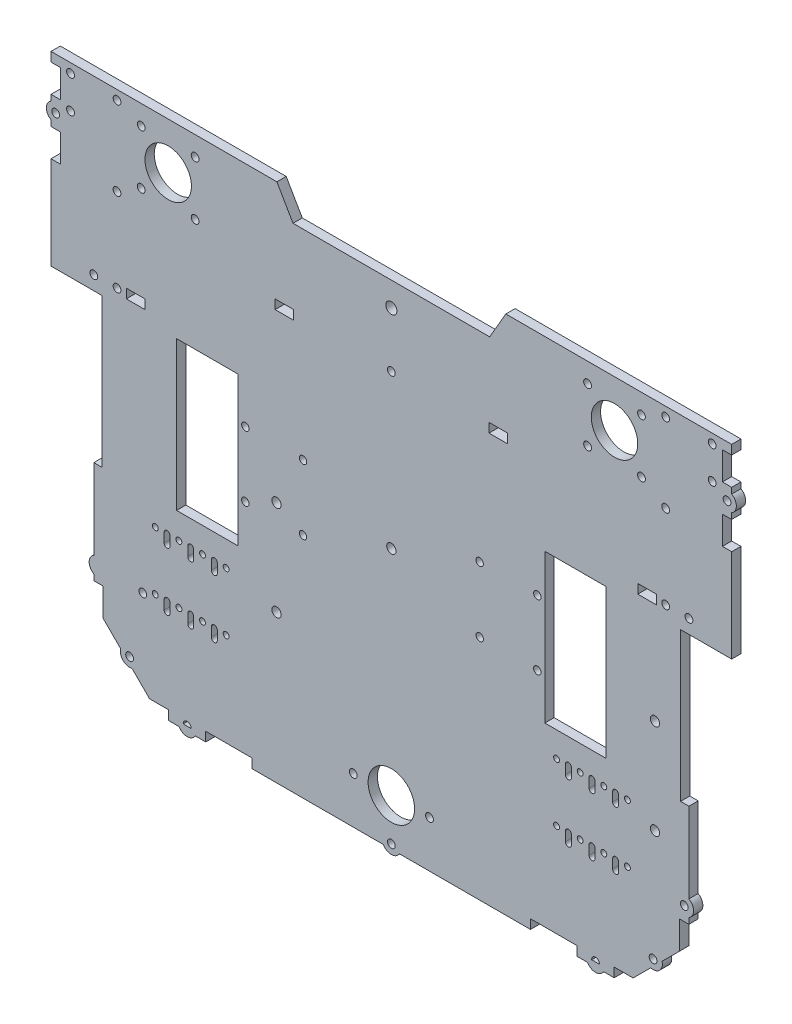
SolidWorks part; units mm, degrees
ref_plane "Front Plane" through (0, 0, 0) normal (0, 0, 1) x (1, 0, 0)
ref_plane "Top Plane" through (0, 0, 0) normal (0, 1, 0) x (1, 0, 0)
ref_plane "Right Plane" through (0, 0, 0) normal (1, 0, 0) x (0, 0, -1)
sketch "Sketch1" plane through (0, 0, 0) normal (0, 0, 1) x (1, 0, 0)
  line L0 (25.4788, 82.9173) -> (-48.0827, -25.4788) construction
  line L1 (0, 0) -> (-320, 0)
  line L2 (0, 0) -> (0, 280)
  line L3 (0, 280) -> (-320, 280)
  line L4 (-320, 0) -> (-320, 280)
  line L5 (-287.2977, 295.1787) -> (-360.8591, 186.7826) construction
  line L6 (25.4788, 82.9173) -> (-287.2977, 295.1787) construction
  line L13 (-184.6572, -15.1656) -> (-182.9535, -19.8663) construction
  line L14 (-182.9535, -19.8663) -> (-121.3306, 2.4686) construction
  line L18 (-114.8924, 10.1204) -> (-184.6572, -15.1656) construction
  line L20 (-48.0827, -25.4788) -> (-360.8591, 186.7826) construction
  line L21 (-46.3981, -22.9964) -> (-359.1745, 189.265) construction
  line L22 (23.7942, 80.4349) -> (-288.9823, 292.6963) construction
  line L23 (-184.6572, -15.1656) -> (-186.361, -10.4648) construction
  line L24 (-186.361, -10.4648) -> (-124.7382, 11.8702) construction
  line L36 (-185.5509, 222.5041) -> (-255.7432, 119.0727) construction
  line L37 (-117.2157, 100.5961) -> (-220.647, 170.7884) construction
  line L38 (-82.1195, 152.3118) -> (-152.3118, 48.8805) construction
  circle A0 centre (-65.5, 65.5) radius 62.5 construction
  circle A17 centre (-272.3627, 205.8845) radius 62.5 construction
  circle A18 centre (-65.5, 65.5) radius 65.5 construction
  circle A22 centre (-168.9314, 135.6923) radius 62.5 construction
  circle A24 centre (-114.8924, 10.1204) radius 74.2059 construction
  circle A27 centre (-114.8924, 10.1204) radius 2.5 construction
  circle A28 centre (-138.3962, 1.6016) radius 1.5 construction
  arc A29 (-121.3306, 2.4686) -> (-124.7382, 11.8702) centre (-114.8924, 10.1204) ccw construction
  point P8 (-320, 246.3436)
  point P9 (-320, 165.4254)
  point P15 (0, 0)
  point P18 (-399.3278, -71.3874)
  point P19 (0, 0)
  point P26 (0, 0)
  point P32 (0, 0)
  point P33 (-297.9462, 157.5259)
  point P34 (-114.3385, 11.0623)
  point P35 (0, 0)
  point P36 (-114.8924, 10.1204)
  dimension "D5" = 5
  dimension "D6" = 5
  dimension "D11" = 125
  dimension "D12" = 280
  dimension "D26" = 125
  dimension "D31" = 125
  dimension "D4" = 5
  dimension "D9" = 10
  dimension "D13" = 320
  dimension "D8" = 3
  dimension "D10" = 3
  dimension "D7" = 25
extrude "Boss-Extrude1" add sketch "Sketch1" along normal blind 5
sketch "Sketch2" plane through (0, 0, 5) normal (0, 0, 1) x (1, 0, 0)
  line L0 (-320, 280) -> (-320, 0) construction
  line L1 (-320, 180) -> (-242.5, 180)
  line L2 (-320, 180) -> (-320, 100)
  line L3 (-320, 100) -> (-242.5, 100)
  line L4 (-242.5, 180) -> (-242.5, 100)
  line L5 (-160, 280) -> (-160, 182.7983) construction
  line L6 (0, 280) -> (-320, 280) construction
  line L7 (-77.5, 180) -> (-77.5, 100)
  line L8 (0, 100) -> (-77.5, 100)
  line L9 (0, 180) -> (0, 100)
  line L10 (0, 180) -> (-77.5, 180)
  point P14 (-320, 140)
  point P15 (-242.5, 140)
  dimension "D1" = 80
  dimension "D2" = 77.5
extrude "Cut-Extrude1" cut sketch "Sketch2" against normal blind 5
sketch "Sketch3" plane through (0, 0, 5) normal (0, 0, 1) x (1, 0, 0)
  line L0 (-242.5, 180) -> (-320, 180) construction
  line L1 (-310.5, 180) -> (-293, 180)
  line L2 (-310.5, 180) -> (-310.5, 100)
  line L3 (-310.5, 100) -> (-293, 100)
  line L4 (-293, 180) -> (-293, 100)
  line L5 (-320, 100) -> (-242.5, 100) construction
  line L6 (-242.5, 100) -> (-242.5, 180) construction
  line L7 (-160, 280) -> (-160, 181.1057) construction
  line L8 (0, 280) -> (-320, 280) construction
  line L9 (-27, 180) -> (-27, 100)
  line L10 (-9.5, 100) -> (-27, 100)
  line L11 (-9.5, 180) -> (-9.5, 100)
  line L12 (-9.5, 180) -> (-27, 180)
  dimension "D1" = 17.5
  dimension "D2" = 68
extrude "Boss-Extrude2" add sketch "Sketch3" against normal blind 5
ref_plane "Plane1" through (-160, 0, 0) normal (1, 0, 0) x (0, 0, -1)
sketch "Sketch9" plane through (0, 0, 0) normal (0, 0, -1) x (-1, 0, 0)
  line L0 (320, 0) -> (0, 0) construction
  line L1 (210, 260) -> (260, 346.6025)
  line L2 (260, 346.6025) -> (210, 433.2051)
  line L3 (210, 433.2051) -> (110, 433.2051)
  line L4 (110, 433.2051) -> (60, 346.6025)
  line L5 (60, 346.6025) -> (110, 260)
  line L6 (110, 260) -> (210, 260)
  line L8 (0, 280) -> (320, 280) construction
  circle A0 centre (160, 346.6025) radius 86.6025 construction
  point P11 (160, 0)
  dimension "D1" = 200
  dimension "D2" = 20
extrude "Cut-Extrude8" cut sketch "Sketch9" against normal blind 5
sketch "Sketch10" plane through (-320, 0, 0) normal (-1, 0, 0) x (0, 0, 1)
  line L4 (0, 280) -> (0, 180)
  line L5 (0, 180) -> (5, 180)
  line L6 (5, 180) -> (5, 280)
  line L7 (5, 280) -> (0, 280)
  line L8 (0, 280) -> (0, 180)
  line L9 (0, 180) -> (5, 180)
  line L10 (5, 180) -> (5, 280)
  line L11 (5, 280) -> (0, 280)
  dimension "D1" = 0
extrude "Boss-Extrude3" add sketch "Sketch10" along normal blind 20
mirror "Mirror2" about plane through (-160, 0, 0) normal (1, 0, 0) of "Boss-Extrude3"
sketch "Sketch5" plane through (0, 0, 5) normal (0, 0, 1) x (1, 0, 0)
  line L0 (20, 280) -> (-98.453, 280) construction
  line L3 (12.5, 257.5) -> (0, 245) construction
  line L4 (0, 245) -> (24.9281, 220.0719) construction
  line L5 (20, 280) -> (20, 180) construction
  circle A1 centre (0, 245) radius 11 construction
  circle A2 centre (12.5, 257.5) radius 2.1
  circle A5 centre (-12.5, 232.5) radius 2.1
  circle A6 centre (-12.5, 187.5) radius 2.1
  circle A7 centre (12.5, 162.5) radius 2.1
  circle A8 centre (-57.5, 187.5) radius 2.1
  circle A9 centre (-82.5, 162.5) radius 2.1
  circle A10 centre (-57.5, 232.5) radius 2.1
  circle A11 centre (-82.5, 257.5) radius 2.1
  circle A12 centre (-12.5, 275) radius 2.1
  circle A13 centre (12.5, 275) radius 2.1
  dimension "D1" = 35
  dimension "D2" = 12.5
  dimension "D3" = 12.5
  dimension "D4" = 22
  dimension "D5" = 4
  dimension "D6" = 4.2
  dimension "D7" = 5
  dimension "D8" = 20
  dimension "D9" = 5
  dimension "D10" = 4.2
  dimension "D11" = 4.2
  dimension "D12" = 12.5
  dimension "D13" = 12.5
extrude "Cut-Extrude9" cut sketch "Sketch5" against normal blind 10 contours A1 | A6 | A12 | A7 | A5 | A2 | A13 region at (-12.5, 232.5, 5) region at (-12.5, 187.5, 5) region at (12.5, 162.5, 5) region at (-12.5, 275, 5)
mirror "Mirror3" about plane through (-160, 0, 0) normal (1, 0, 0) of "Cut-Extrude9"
sketch "Sketch12" plane through (0, 0, 5) normal (0, 0, 1) x (1, 0, 0)
  line L0 (0, 0) -> (0, 100) construction
  line L1 (0, 10) -> (-5, 10)
  line L2 (0, 10) -> (0, 45.2)
  line L3 (0, 45.2) -> (-5, 45.2)
  line L4 (-5, 10) -> (-5, 45.2)
  line L5 (-320, 0) -> (0, 0) construction
  line L6 (-160, -2.75) -> (-160, 2.75) construction
  line L7 (-320, 45.2) -> (-315, 45.2)
  line L8 (-315, 10) -> (-315, 45.2)
  line L9 (-320, 10) -> (-315, 10)
  line L10 (-320, 10) -> (-320, 45.2)
  line L11 (-320, 100) -> (-320, 0) construction
  line L12 (-295, 0) -> (-234.8, 0)
  line L13 (-295, 0) -> (-295, 5)
  line L14 (-295, 5) -> (-234.8, 5)
  line L15 (-234.8, 0) -> (-234.8, 5)
  line L16 (-25, 5) -> (-85.2, 5)
  line L17 (-85.2, 0) -> (-85.2, 5)
  line L18 (-25, 0) -> (-85.2, 0)
  line L19 (-25, 0) -> (-25, 5)
  dimension "D1" = 35.2
  dimension "D2" = 5
  dimension "D3" = 10
  dimension "D4" = 5
  dimension "D5" = 60.2
  dimension "D6" = 25
extrude "Cut-Extrude11" cut sketch "Sketch12" against normal blind 10
sketch "Sketch15" plane through (0, 0, 0) normal (0, 0, -1) x (-1, 0, 0)
  line L0 (242.5, 140) -> (150.9995, 140) construction
  line L1 (242.5, 100) -> (242.5, 180) construction
  line L2 (223, 87.5) -> (223, 97.0195) construction
  line L3 (242.5, 100) -> (77.5, 100) construction
  line L4 (160, 100) -> (160, 101.8451) construction
  line L5 (97, 87.5) -> (97, 97.0195) construction
  line L6 (77.5, 140) -> (169.0005, 140) construction
  circle A0 centre (238.5, 122.5) radius 2
  circle A1 centre (238.5, 157.5) radius 2
  circle A2 centre (207.5, 157.5) radius 2
  circle A3 centre (207.5, 122.5) radius 2
  circle A4 centre (112.5, 122.5) radius 2
  circle A5 centre (112.5, 157.5) radius 2
  circle A6 centre (81.5, 157.5) radius 2
  circle A7 centre (81.5, 122.5) radius 2
  circle A8 centre (160, 140) radius 2.5
  point P6 (242.5, 140)
  dimension "D1" = 4
  dimension "D2" = 4
  dimension "D3" = 17.5
  dimension "D5" = 5
  dimension "D4" = 15.5
extrude "Cut-Extrude13" cut sketch "Sketch15" against normal blind 10
sketch "Sketch16" plane through (0, 0, 0) normal (0, 0, -1) x (-1, 0, 0)
  line L0 (27, 145) -> (9.5, 145) construction
  line L1 (9.5, 65) -> (27, 65) construction
  line L2 (18.25, 145) -> (18.25, 65) construction
  line L3 (18.25, 105) -> (30.55, 105) construction
  line L4 (120, 105) -> (120, 123.3727) construction
  line L5 (221.75, 105) -> (209.45, 105) construction
  circle A4 centre (18.25, 130.5) radius 2.5
  circle A5 centre (18.25, 79.5) radius 2.5
  circle A6 centre (221.75, 79.5) radius 2.5
  circle A7 centre (221.75, 130.5) radius 2.5
  point P12 (18.25, 105)
  dimension "D1" = 5
  dimension "D2" = 25.5
extrude "Cut-Extrude14" cut sketch "Sketch16" against normal blind 10
sketch "Sketch17" plane through (0, 0, 0) normal (0, 0, -1) x (-1, 0, 0)
  line L0 (40, 255) -> (92.7701, 202.2299) construction
  line L1 (-20, 280) -> (98.453, 280) construction
  line L2 (-20, 280) -> (-20, 180) construction
  line L3 (40, 255) -> (-1.2922, 213.7078) construction
  line L4 (160, 260) -> (160, 162.3502) construction
  line L5 (110, 260) -> (210, 260) construction
  line L6 (280, 255) -> (321.2922, 213.7078) construction
  line L7 (280, 255) -> (227.2299, 202.2299) construction
  line L8 (280, 255) -> (321.2922, 213.7078) construction
  line L9 (280, 255) -> (227.2299, 202.2299) construction
  circle A0 centre (40, 255) radius 12.5
  circle A1 centre (54.4957, 240.5043) radius 2.1
  circle A2 centre (25.5043, 269.4957) radius 2.1
  circle A12 centre (54.4957, 269.4957) radius 2.1
  circle A13 centre (25.5043, 240.5043) radius 2.1
  circle A14 centre (54.4957, 240.5043) radius 2.1
  circle A15 centre (25.5043, 269.4957) radius 2.1
  circle A16 centre (25.5043, 240.5043) radius 2.1
  circle A17 centre (54.4957, 269.4957) radius 2.1
  circle A18 centre (265.5043, 269.4957) radius 2.1
  circle A19 centre (294.4957, 240.5043) radius 2.1
  circle A20 centre (294.4957, 269.4957) radius 2.1
  circle A21 centre (265.5043, 240.5043) radius 2.1
  circle A22 centre (294.4957, 240.5043) radius 2.1
  circle A23 centre (265.5043, 269.4957) radius 2.1
  circle A24 centre (280, 255) radius 12.5
  circle A25 centre (265.5043, 240.5043) radius 2.1
  circle A26 centre (294.4957, 269.4957) radius 2.1
  dimension "D1" = 25
  dimension "D2" = 4.2
  dimension "D3" = 20.5
  dimension "D4" = 25
  dimension "D5" = 60
  dimension "D6" = 45
  dimension "D7" = 4
extrude "Cut-Extrude15" cut sketch "Sketch17" against normal blind 5 contours A13 | A0 | A13 | A12 | A1 | A24 | A20 | A19 | A21 | A2 | A18 region at (-40, 255, 0) region at (-54.4957, 240.5043, 0) region at (-54.4957, 269.4957, 0) region at (-25.5043, 240.5043, 0) region at (-294.4957, 240.5043, 0) region at (-294.4957, 269.4957, 0) region at (-265.5043, 240.5043, 0) region at (-280, 255, 0)
sketch "Sketch18" plane through (0, 0, 5) normal (0, 0, 1) x (1, 0, 0)
  line L0 (-315, 30) -> (-290, 5)
  line L1 (-315, 10) -> (-315, 45.2) construction
  line L2 (-234.8, 5) -> (-295, 5) construction
  line L3 (-290, 5) -> (-315, 5)
  line L4 (-315, 5) -> (-315, 30)
  line L5 (-315, 10) -> (-320, 10)
  line L6 (-320, 10) -> (-320, 0)
  line L7 (-320, 0) -> (-295, 0)
  line L8 (-295, 0) -> (-295, 5)
  line L9 (-160, -2.75) -> (-160, 2.75) construction
  line L10 (-5, 5) -> (-5, 30)
  line L11 (-5, 30) -> (-30, 5)
  line L12 (-25, 0) -> (-25, 5)
  line L13 (0, 0) -> (-25, 0)
  line L14 (0, 10) -> (0, 0)
  line L15 (-5, 10) -> (0, 10)
  line L16 (-30, 5) -> (-5, 5)
  dimension "D1" = 25
  dimension "D2" = 25
extrude "Cut-Extrude17" cut sketch "Sketch18" against normal blind 10 contours L4 L3 L0 | L7 L8 L3 L4 L5 L6 | L11 L16 L10 | L16 L12 L13 L14 L15 L10 region at (-306.6667, 13.3333, 5) region at (-309.1667, 3.3333, 5) region at (-13.3333, 13.3333, 5) region at (-10.8333, 3.3333, 5)
sketch "Sketch19" plane through (0, 0, 0) normal (0, 0, -1) x (-1, 0, 0)
  line L0 (234.8, 0) -> (85.2, 0) construction
  line L1 (166.1126, 25) -> (84.2471, 25) construction
  line L2 (160, 25) -> (160, 31.0152) construction
  circle A0 centre (160, 25) radius 12.5
  circle A2 centre (139.5, 25) radius 2.1
  circle A4 centre (180.5, 25) radius 2.1
  point P4 (160, 0)
  dimension "D1" = 25
  dimension "D2" = 25
  dimension "D3" = 4.2
  dimension "D4" = 20.5
extrude "Cut-Extrude18" cut sketch "Sketch19" against normal blind 10
sketch "Sketch21" plane through (-340, 0, 0) normal (-1, 0, 0) x (0, 0, 1)
  line L4 (5, 280) -> (0, 280)
  line L5 (0, 280) -> (0, 180)
  line L6 (0, 180) -> (5, 180)
  line L7 (5, 180) -> (5, 280)
  line L8 (5, 280) -> (0, 280)
  line L9 (0, 280) -> (0, 180)
  line L10 (0, 180) -> (5, 180)
  line L11 (5, 180) -> (5, 280)
  dimension "D1" = 0
extrude "Cut-Extrude20" cut sketch "Sketch21" against normal blind 3
sketch "Sketch22" plane through (20, 0, 0) normal (1, 0, 0) x (0, 0, -1)
  line L4 (0, 280) -> (-5, 280)
  line L5 (-5, 280) -> (-5, 180)
  line L6 (-5, 180) -> (0, 180)
  line L7 (0, 180) -> (0, 280)
  line L8 (0, 280) -> (-5, 280)
  line L9 (-5, 280) -> (-5, 180)
  line L10 (-5, 180) -> (0, 180)
  line L11 (0, 180) -> (0, 280)
  dimension "D1" = 0
extrude "Cut-Extrude21" cut sketch "Sketch22" against normal blind 3
sketch "Sketch23" plane through (0, 0, 0) normal (0, 0, -1) x (-1, 0, 0)
  line L0 (234.8, 0) -> (85.2, 0) construction
  line L1 (164.3301, 0) -> (155.6699, 0) construction
  circle A0 centre (160, 2.5) radius 2.1
  arc A1 (164.3301, 0) -> (155.6699, 0) centre (160, 2.5) cw construction
  point P5 (160, 0)
  dimension "D1" = 4.2
  dimension "D2" = 2.5
  dimension "D3" = 5
extrude "Cut-Extrude22" cut sketch "Sketch23" against normal blind 10
sketch "Sketch24" plane through (0, 0, 0) normal (0, 0, -1) x (-1, 0, 0)
  line L0 (234.8, 0) -> (85.2, 0) construction
  line L1 (164.3301, 0) -> (155.6699, 0)
  arc A0 (164.3301, 0) -> (155.6699, 0) centre (160, 2.5) cw
  dimension "D1" = 5
extrude "Boss-Extrude4" add sketch "Sketch24" against normal blind 5
sketch "Sketch25" plane through (-17.5, 17.5, 0) normal (0.7071, -0.7071, 0) x (0, 0, -1)
  line L1 (12.2918, -37.7929) -> (-20.8331, -37.7929)
  line L2 (12.2918, -37.7929) -> (12.2918, 35.3561)
  line L3 (12.2918, 35.3561) -> (-20.8331, 35.3561)
  line L4 (-20.8331, -37.7929) -> (-20.8331, 35.3561)
ref_plane "Plane2" through (-160, 0, 0) normal (1, 0, 0) x (0, 0, -1)
sketch "Sketch26" plane through (0, 5, 0) normal (0, -1, 0) x (1, 0, 0)
  line L1 (-60.2, 5) -> (-40.2, 5)
  line L2 (-60.2, 5) -> (-60.2, 0)
  line L3 (-60.2, 0) -> (-40.2, 0)
  line L4 (-40.2, 5) -> (-40.2, 0)
  line L7 (-85.2, 0) -> (-85.2, 5) construction
  line L8 (-164.3301, 5) -> (-164.3301, 0) construction
  line L12 (-155.6699, 5) -> (-155.6699, 0) construction
  line L13 (-164.3301, 5) -> (-164.3301, 0) construction
  line L14 (-155.6699, 5) -> (-155.6699, 0) construction
  line L16 (-155.6699, 2.5) -> (-164.3301, 2.5) construction
  line L17 (-164.3301, 2.5) -> (-160, 2.5) construction
  line L18 (-160, 2.5) -> (-160, 11.7083) construction
  line L19 (-279.8, 5) -> (-279.8, 0)
  line L20 (-259.8, 0) -> (-279.8, 0)
  line L21 (-259.8, 5) -> (-259.8, 0)
  line L22 (-259.8, 5) -> (-279.8, 5)
  line M6 (-30, 5) -> (-85.2, 5)
  line M8 (-85.2, 0) -> (-30, 0)
  dimension "D1" = 20
  dimension "D2" = 25
extrude "Boss-Extrude5" add sketch "Sketch26" along normal blind 5 contours L4 L2 M6 M8 | L21 L22 L19 L20 region at (-50.2, 5, 2.5) region at (-269.8, 5, 2.5)
sketch "Sketch27" plane through (0, 0, 0) normal (0, 0, -1) x (-1, 0, 0)
  line L2 (160, 2.5) -> (160, 6.3371) construction
  circle A0 centre (50.2, 2.5) radius 2.1
  circle A1 centre (269.8, 2.5) radius 2.1
  dimension "D3" = 4.2
extrude "Cut-Extrude24" cut sketch "Sketch27" against normal blind 5
sketch "Sketch29" plane through (0, 0, 0) normal (0, 0, -1) x (-1, 0, 0)
  line L1 (274.7978, 2.3518) -> (264.8022, 2.3518)
  line L2 (160, 2.75) -> (160, -2.75) construction
  line L3 (45.2022, 2.3518) -> (55.1978, 2.3518)
  arc A0 (264.8022, 2.3518) -> (274.7978, 2.3518) centre (269.8, 2.5) ccw
  arc A1 (55.1978, 2.3518) -> (45.2022, 2.3518) centre (50.2, 2.5) cw
  dimension "D1" = 5
extrude "Boss-Extrude7" add sketch "Sketch29" against normal blind 5
sketch "Sketch30" plane through (-9.5, 0, 0) normal (1, 0, 0) x (0, 0, -1)
  line L4 (-5, 180) -> (-5, 100)
  line L6 (-5, 180) -> (-5, 100)
  line L12 (-5, 100) -> (0, 100)
  line L14 (-5, 100) -> (0, 100)
  line L16 (0, 100) -> (0, 180)
  line L17 (0, 100) -> (0, 180)
  line L18 (0, 180) -> (-5, 180)
  line L19 (0, 180) -> (-5, 180)
  dimension "D1" = 0
extrude "Boss-Extrude8" add sketch "Sketch30" along normal blind 5
sketch "Sketch31" plane through (-310.5, 0, 0) normal (-1, 0, 0) x (0, 0, 1)
  line L4 (5, 100) -> (5, 180)
  line L5 (5, 180) -> (0, 180)
  line L6 (0, 180) -> (0, 100)
  line L8 (5, 100) -> (5, 180)
  line L10 (0, 180) -> (0, 100)
  line L12 (5, 180) -> (0, 180)
  line L14 (0, 100) -> (5, 100)
  line L15 (0, 100) -> (5, 100)
  dimension "D1" = 0
extrude "Boss-Extrude9" add sketch "Sketch31" along normal blind 5
sketch "Sketch32" plane through (0, 0, 0) normal (0, 0, -1) x (-1, 0, 0)
  line L0 (5, 30) -> (30, 5) construction
  line L1 (17.5, 17.5) -> (24.3538, 24.3538) construction
  circle A0 centre (19.2678, 19.2678) radius 2.1
  dimension "D1" = 4.2
  dimension "D2" = 2.5
extrude "Cut-Extrude25" cut sketch "Sketch32" against normal blind 5
sketch "Sketch33" plane through (0, 0, 0) normal (0, 0, -1) x (-1, 0, 0)
  line L0 (5, 30) -> (30, 5) construction
  line L1 (20.5619, 14.4381) -> (14.4381, 20.5619)
  arc A0 (20.5619, 14.4381) -> (14.4381, 20.5619) centre (19.2678, 19.2678) cw
  dimension "D1" = 5
extrude "Boss-Extrude10" add sketch "Sketch33" against normal blind 5
ref_plane "Plane3" through (-160, 0, 0) normal (-1, 0, 0) x (0, 0, 1)
mirror "Mirror4" about plane through (-160, 0, 0) normal (-1, 0, 0) of "Boss-Extrude10", "Cut-Extrude25"
sketch "Sketch34" plane through (0, 0, 5) normal (0, 0, 1) x (1, 0, 0)
  line L2 (-110, 260) -> (-210, 260) construction
  circle A0 centre (-160, 252) radius 3
  point P4 (-160, 260)
  dimension "D1" = 6
  dimension "D3" = 8
extrude "Cut-Extrude26" cut sketch "Sketch34" against normal blind 5
sketch "Sketch35" plane through (0, 0, 0) normal (0, 0, -1) x (-1, 0, 0)
  line L0 (110, 260) -> (210, 260) construction
  line L1 (97.5, 225) -> (107.5, 225)
  line L2 (97.5, 225) -> (97.5, 220)
  line L3 (97.5, 220) -> (107.5, 220)
  line L4 (107.5, 225) -> (107.5, 220)
  line L5 (-17, 180) -> (-17, 280) construction
  line L6 (160, 260) -> (160, 169.3293) construction
  line L7 (212.5, 225) -> (212.5, 220)
  line L8 (222.5, 220) -> (212.5, 220)
  line L9 (222.5, 225) -> (222.5, 220)
  line L10 (222.5, 225) -> (212.5, 225)
  line L11 (107.5, 222.5) -> (212.5, 222.5) construction
  circle A0 centre (160, 222.5) radius 2.1
  point P6 (97.5, 222.5)
  dimension "D5" = 4.2
  dimension "D1" = 35
  dimension "D2" = 114.5
  dimension "D3" = 10
  dimension "D4" = 5
extrude "Cut-Extrude27" cut sketch "Sketch35" against normal blind 5
sketch "Sketch37" plane through (0, 45.2, 0) normal (0, -1, 0) x (1, 0, 0)
  line L4 (0, 0) -> (0, 5)
  line L5 (0, 5) -> (-5, 5)
  line L6 (-5, 5) -> (-5, 0)
  line L7 (-5, 0) -> (0, 0)
  line L8 (0, 0) -> (0, 5)
  line L9 (0, 5) -> (-5, 5)
  line L10 (-5, 5) -> (-5, 0)
  line L11 (-5, 0) -> (0, 0)
  dimension "D1" = 0
extrude "Boss-Extrude11" add sketch "Sketch37" along normal blind 0.2
sketch "Sketch38" plane through (0, 45.2, 0) normal (0, -1, 0) x (1, 0, 0)
  line L4 (-315, 0) -> (-315, 5)
  line L5 (-315, 5) -> (-320, 5)
  line L6 (-320, 5) -> (-320, 0)
  line L7 (-320, 0) -> (-315, 0)
  line L8 (-315, 0) -> (-315, 5)
  line L9 (-315, 5) -> (-320, 5)
  line L10 (-320, 5) -> (-320, 0)
  line L11 (-320, 0) -> (-315, 0)
  dimension "D1" = 0
extrude "Boss-Extrude12" add sketch "Sketch38" along normal blind 0.2
sketch "Sketch39" plane through (0, 0, 0) normal (0, 0, -1) x (-1, 0, 0)
  line L0 (5, 45) -> (0, 45) construction
  line L1 (0, 45) -> (0, 100) construction
  line L2 (148.069, 28.7284) -> (148.069, 57.8422) construction
  line L3 (0, 56.8301) -> (0, 48.1699) construction
  line L4 (296.138, 56.8301) -> (296.138, 48.1699) construction
  circle A0 centre (2.5, 52.5) radius 2.1
  circle A1 centre (160, 25) radius 12.5 construction
  circle A2 centre (293.638, 52.5) radius 2.1
  arc A3 (0, 48.1699) -> (0, 56.8301) centre (2.5, 52.5) cw construction
  arc A4 (296.138, 48.1699) -> (296.138, 56.8301) centre (293.638, 52.5) ccw construction
  dimension "D1" = 4.2
  dimension "D2" = 7.5
  dimension "D3" = 2.5
  dimension "D4" = 5
extrude "Cut-Extrude28" cut sketch "Sketch39" against normal blind 5
sketch "Sketch40" plane through (0, 0, 0) normal (0, 0, -1) x (-1, 0, 0)
  line L0 (0, 45) -> (0, 100) construction
  line L1 (0, 56.8301) -> (0, 48.1699)
  line L2 (160, 37.5) -> (160, 52.5) construction
  line L3 (320, 56.8301) -> (320, 48.1699)
  arc A0 (0, 48.1699) -> (0, 56.8301) centre (2.5, 52.5) cw
  circle A1 centre (160, 25) radius 12.5 construction
  arc A2 (320, 48.1699) -> (320, 56.8301) centre (317.5, 52.5) ccw
  dimension "D1" = 5
extrude "Boss-Extrude13" add sketch "Sketch40" against normal blind 5
sketch "Sketch42" plane through (0, 0, 5) normal (0, 0, 1) x (1, 0, 0)
  line L0 (-81.5, 157.5) -> (-81.5, 122.5) construction
  line L1 (-81.5, 140) -> (-63.225, 140) construction
  line L2 (-71.1625, 86.5) -> (-71.1625, 55.25) construction
  line L3 (-71.1625, 70.875) -> (-81.5, 70.875) construction
  line L4 (-64.8125, 86.5) -> (-64.8125, 55.25) construction
  line L5 (-58.4625, 86.5) -> (-58.4625, 55.25) construction
  line L6 (-52.1125, 55.25) -> (-52.1125, 86.5) construction
  line L7 (-45.7625, 86.5) -> (-45.7625, 55.25) construction
  line L8 (-39.4125, 55.25) -> (-39.4125, 86.5) construction
  line L9 (-33.0625, 86.5) -> (-33.0625, 55.25) construction
  line L10 (17, 280) -> (17, 180) construction
  line L13 (17, 280) -> (-98.453, 280) construction
  line L14 (-64.8125, 86.5) -> (-64.8125, 81.5) construction
  line L15 (-63.225, 86.5) -> (-63.225, 81.5)
  line L16 (-66.4, 86.5) -> (-66.4, 81.5)
  line L17 (-52.1125, 86.5) -> (-52.1125, 81.5) construction
  line L18 (-50.525, 86.5) -> (-50.525, 81.5)
  line L19 (-53.7, 86.5) -> (-53.7, 81.5)
  line L20 (-39.4125, 86.5) -> (-39.4125, 81.5) construction
  line L21 (-37.825, 86.5) -> (-37.825, 81.5)
  line L22 (-41, 86.5) -> (-41, 81.5)
  line L23 (-64.8125, 55.25) -> (-64.8125, 50.25) construction
  line L24 (-63.225, 55.25) -> (-63.225, 50.25)
  line L25 (-66.4, 55.25) -> (-66.4, 50.25)
  line L26 (-52.1125, 55.25) -> (-52.1125, 50.25) construction
  line L27 (-50.525, 55.25) -> (-50.525, 50.25)
  line L28 (-53.7, 55.25) -> (-53.7, 50.25)
  line L29 (-39.4125, 55.25) -> (-39.4125, 50.25) construction
  line L30 (-37.825, 55.25) -> (-37.825, 50.25)
  line L31 (-41, 55.25) -> (-41, 50.25)
  line L32 (-160, -2.75) -> (-160, 2.75) construction
  line L33 (-286.9375, 86.5) -> (-286.9375, 55.25) construction
  line L34 (-280.5875, 55.25) -> (-280.5875, 86.5) construction
  line L35 (-274.2375, 86.5) -> (-274.2375, 55.25) construction
  line L36 (-267.8875, 55.25) -> (-267.8875, 86.5) construction
  line L37 (-261.5375, 86.5) -> (-261.5375, 55.25) construction
  line L38 (-255.1875, 86.5) -> (-255.1875, 55.25) construction
  line L39 (-248.8375, 70.875) -> (-238.5, 70.875) construction
  line L40 (-248.8375, 86.5) -> (-248.8375, 55.25) construction
  line L41 (-280.5875, 55.25) -> (-280.5875, 50.25) construction
  line L42 (-282.175, 55.25) -> (-282.175, 50.25)
  line L43 (-279, 55.25) -> (-279, 50.25)
  line L44 (-267.8875, 55.25) -> (-267.8875, 50.25) construction
  line L45 (-269.475, 55.25) -> (-269.475, 50.25)
  line L46 (-266.3, 55.25) -> (-266.3, 50.25)
  line L47 (-255.1875, 55.25) -> (-255.1875, 50.25) construction
  line L48 (-256.775, 55.25) -> (-256.775, 50.25)
  line L49 (-253.6, 55.25) -> (-253.6, 50.25)
  line L50 (-280.5875, 86.5) -> (-280.5875, 81.5) construction
  line L51 (-282.175, 86.5) -> (-282.175, 81.5)
  line L52 (-279, 86.5) -> (-279, 81.5)
  line L53 (-267.8875, 86.5) -> (-267.8875, 81.5) construction
  line L54 (-269.475, 86.5) -> (-269.475, 81.5)
  line L55 (-266.3, 86.5) -> (-266.3, 81.5)
  line L56 (-255.1875, 86.5) -> (-255.1875, 81.5) construction
  line L57 (-256.775, 86.5) -> (-256.775, 81.5)
  line L58 (-253.6, 86.5) -> (-253.6, 81.5)
  arc A2 (-63.225, 86.5) -> (-66.4, 86.5) centre (-64.8125, 86.5) ccw
  arc A3 (-66.4, 81.5) -> (-63.225, 81.5) centre (-64.8125, 81.5) ccw
  arc A4 (-50.525, 86.5) -> (-53.7, 86.5) centre (-52.1125, 86.5) ccw
  arc A5 (-53.7, 81.5) -> (-50.525, 81.5) centre (-52.1125, 81.5) ccw
  arc A6 (-37.825, 86.5) -> (-41, 86.5) centre (-39.4125, 86.5) ccw
  arc A7 (-41, 81.5) -> (-37.825, 81.5) centre (-39.4125, 81.5) ccw
  arc A8 (-63.225, 55.25) -> (-66.4, 55.25) centre (-64.8125, 55.25) ccw
  arc A9 (-66.4, 50.25) -> (-63.225, 50.25) centre (-64.8125, 50.25) ccw
  arc A10 (-50.525, 55.25) -> (-53.7, 55.25) centre (-52.1125, 55.25) ccw
  arc A11 (-53.7, 50.25) -> (-50.525, 50.25) centre (-52.1125, 50.25) ccw
  arc A12 (-37.825, 55.25) -> (-41, 55.25) centre (-39.4125, 55.25) ccw
  arc A13 (-41, 50.25) -> (-37.825, 50.25) centre (-39.4125, 50.25) ccw
  arc A14 (-259.95, 86.5) -> (-263.125, 86.5) centre (-261.5375, 86.5) cw
  arc A15 (-263.125, 86.5) -> (-259.95, 86.5) centre (-261.5375, 86.5) cw
  arc A16 (-253.6, 86.5) -> (-256.775, 86.5) centre (-255.1875, 86.5) cw
  arc A17 (-256.775, 86.5) -> (-253.6, 86.5) centre (-255.1875, 86.5) cw
  arc A18 (-247.25, 86.5) -> (-250.425, 86.5) centre (-248.8375, 86.5) cw
  arc A19 (-250.425, 86.5) -> (-247.25, 86.5) centre (-248.8375, 86.5) cw
  arc A20 (-269.475, 86.5) -> (-266.3, 86.5) centre (-267.8875, 86.5) cw
  arc A21 (-266.3, 86.5) -> (-269.475, 86.5) centre (-267.8875, 86.5) cw
  arc A22 (-275.825, 86.5) -> (-272.65, 86.5) centre (-274.2375, 86.5) cw
  arc A23 (-272.65, 86.5) -> (-275.825, 86.5) centre (-274.2375, 86.5) cw
  arc A24 (-282.175, 86.5) -> (-279, 86.5) centre (-280.5875, 86.5) cw
  arc A25 (-279, 86.5) -> (-282.175, 86.5) centre (-280.5875, 86.5) cw
  arc A26 (-285.35, 86.5) -> (-288.525, 86.5) centre (-286.9375, 86.5) cw
  arc A27 (-288.525, 86.5) -> (-285.35, 86.5) centre (-286.9375, 86.5) cw
  arc A28 (-69.575, 55.25) -> (-72.75, 55.25) centre (-71.1625, 55.25) ccw
  arc A29 (-72.75, 55.25) -> (-69.575, 55.25) centre (-71.1625, 55.25) ccw
  arc A30 (-63.225, 55.25) -> (-66.4, 55.25) centre (-64.8125, 55.25) ccw
  arc A31 (-66.4, 55.25) -> (-63.225, 55.25) centre (-64.8125, 55.25) ccw
  arc A32 (-56.875, 55.25) -> (-60.05, 55.25) centre (-58.4625, 55.25) ccw
  arc A33 (-60.05, 55.25) -> (-56.875, 55.25) centre (-58.4625, 55.25) ccw
  arc A34 (-50.525, 55.25) -> (-53.7, 55.25) centre (-52.1125, 55.25) ccw
  arc A35 (-53.7, 55.25) -> (-50.525, 55.25) centre (-52.1125, 55.25) ccw
  arc A36 (-44.175, 55.25) -> (-47.35, 55.25) centre (-45.7625, 55.25) ccw
  arc A37 (-47.35, 55.25) -> (-44.175, 55.25) centre (-45.7625, 55.25) ccw
  arc A38 (-37.825, 55.25) -> (-41, 55.25) centre (-39.4125, 55.25) ccw
  arc A39 (-41, 55.25) -> (-37.825, 55.25) centre (-39.4125, 55.25) ccw
  arc A40 (-31.475, 55.25) -> (-34.65, 55.25) centre (-33.0625, 55.25) ccw
  arc A41 (-34.65, 55.25) -> (-31.475, 55.25) centre (-33.0625, 55.25) ccw
  arc A42 (-31.475, 86.5) -> (-34.65, 86.5) centre (-33.0625, 86.5) ccw
  arc A43 (-34.65, 86.5) -> (-31.475, 86.5) centre (-33.0625, 86.5) ccw
  arc A44 (-41, 86.5) -> (-37.825, 86.5) centre (-39.4125, 86.5) ccw
  arc A45 (-37.825, 86.5) -> (-41, 86.5) centre (-39.4125, 86.5) ccw
  arc A46 (-47.35, 86.5) -> (-44.175, 86.5) centre (-45.7625, 86.5) ccw
  arc A47 (-44.175, 86.5) -> (-47.35, 86.5) centre (-45.7625, 86.5) ccw
  arc A48 (-53.7, 86.5) -> (-50.525, 86.5) centre (-52.1125, 86.5) ccw
  arc A49 (-50.525, 86.5) -> (-53.7, 86.5) centre (-52.1125, 86.5) ccw
  arc A50 (-69.575, 86.5) -> (-72.75, 86.5) centre (-71.1625, 86.5) ccw
  arc A51 (-72.75, 86.5) -> (-69.575, 86.5) centre (-71.1625, 86.5) ccw
  arc A52 (-63.225, 86.5) -> (-66.4, 86.5) centre (-64.8125, 86.5) ccw
  arc A53 (-66.4, 86.5) -> (-63.225, 86.5) centre (-64.8125, 86.5) ccw
  arc A54 (-56.875, 86.5) -> (-60.05, 86.5) centre (-58.4625, 86.5) ccw
  arc A55 (-60.05, 86.5) -> (-56.875, 86.5) centre (-58.4625, 86.5) ccw
  arc A56 (-285.35, 55.25) -> (-288.525, 55.25) centre (-286.9375, 55.25) cw
  arc A57 (-288.525, 55.25) -> (-285.35, 55.25) centre (-286.9375, 55.25) cw
  arc A58 (-279, 55.25) -> (-282.175, 55.25) centre (-280.5875, 55.25) cw
  arc A59 (-282.175, 55.25) -> (-279, 55.25) centre (-280.5875, 55.25) cw
  arc A60 (-272.65, 55.25) -> (-275.825, 55.25) centre (-274.2375, 55.25) cw
  arc A61 (-275.825, 55.25) -> (-272.65, 55.25) centre (-274.2375, 55.25) cw
  arc A62 (-266.3, 55.25) -> (-269.475, 55.25) centre (-267.8875, 55.25) cw
  arc A63 (-269.475, 55.25) -> (-266.3, 55.25) centre (-267.8875, 55.25) cw
  arc A64 (-259.95, 55.25) -> (-263.125, 55.25) centre (-261.5375, 55.25) cw
  arc A65 (-263.125, 55.25) -> (-259.95, 55.25) centre (-261.5375, 55.25) cw
  arc A66 (-253.6, 55.25) -> (-256.775, 55.25) centre (-255.1875, 55.25) cw
  arc A67 (-256.775, 55.25) -> (-253.6, 55.25) centre (-255.1875, 55.25) cw
  arc A68 (-247.25, 55.25) -> (-250.425, 55.25) centre (-248.8375, 55.25) cw
  arc A69 (-250.425, 55.25) -> (-247.25, 55.25) centre (-248.8375, 55.25) cw
  arc A70 (-282.175, 55.25) -> (-279, 55.25) centre (-280.5875, 55.25) cw
  arc A71 (-279, 50.25) -> (-282.175, 50.25) centre (-280.5875, 50.25) cw
  arc A72 (-269.475, 55.25) -> (-266.3, 55.25) centre (-267.8875, 55.25) cw
  arc A73 (-266.3, 50.25) -> (-269.475, 50.25) centre (-267.8875, 50.25) cw
  arc A74 (-256.775, 55.25) -> (-253.6, 55.25) centre (-255.1875, 55.25) cw
  arc A75 (-253.6, 50.25) -> (-256.775, 50.25) centre (-255.1875, 50.25) cw
  arc A76 (-282.175, 86.5) -> (-279, 86.5) centre (-280.5875, 86.5) cw
  arc A77 (-279, 81.5) -> (-282.175, 81.5) centre (-280.5875, 81.5) cw
  arc A78 (-269.475, 86.5) -> (-266.3, 86.5) centre (-267.8875, 86.5) cw
  arc A79 (-266.3, 81.5) -> (-269.475, 81.5) centre (-267.8875, 81.5) cw
  arc A80 (-256.775, 86.5) -> (-253.6, 86.5) centre (-255.1875, 86.5) cw
  arc A81 (-253.6, 81.5) -> (-256.775, 81.5) centre (-255.1875, 81.5) cw
  point P22 (-64.8125, 70.875)
  point P23 (-58.4625, 70.875)
  point P28 (-52.1125, 70.875)
  point P29 (-45.7625, 70.875)
  point P34 (-39.4125, 70.875)
  point P35 (-33.0625, 70.875)
  point P52 (-64.8125, 84)
  point P70 (-52.1125, 84)
  point P86 (-39.4125, 84)
  point P92 (-64.8125, 52.75)
  point P98 (-52.1125, 52.75)
  point P104 (-39.4125, 52.75)
  point P158 (-280.5875, 52.75)
  point P162 (-267.8875, 52.75)
  point P166 (-255.1875, 52.75)
  point P170 (-280.5875, 84)
  point P174 (-267.8875, 84)
  point P178 (-255.1875, 84)
  dimension "D1" = 1.5875
  dimension "D10" = 31.25
  dimension "D2" = 36
  dimension "D3" = 50.0625
  dimension "D4" = 56.4125
  dimension "D5" = 62.7625
  dimension "D6" = 69.1125
  dimension "D7" = 75.4625
  dimension "D8" = 81.8125
  dimension "D9" = 88.1625
  dimension "D11" = 5
  dimension "D12" = 5
extrude "Cut-Extrude29" cut sketch "Sketch42" against normal blind 10 contours A6 A44 | A44 L22 A7 L21 | A46 A47 | A4 A48 | A54 A55 | A2 A53 | A50 A51 | A53 L16 A3 L15 | A48 L19 A5 L18 | A43 A42 | A41 A40 | L30 A13 L31 A12 | A37 A36 | L28 A11 L27 A10 | A33 A32 | L25 A9 L24 A8 | A29 A28 region at (-64.8125, 86.5, 5) region at (-64.8125, 82.7532, 5) region at (-52.1125, 86.5, 5) region at (-52.1125, 82.7532, 5) region at (-39.4125, 86.5, 5) region at (-39.4125, 82.7532, 5) region at (-45.7625, 86.5, 5) region at (-71.1625, 86.5, 5) region at (-58.4625, 86.5, 5)
sketch "Sketch43" plane through (-337, 0, 0) normal (-1, 0, 0) x (0, 0, 1)
  line L4 (5, 180) -> (5, 280)
  line L5 (5, 280) -> (0, 280)
  line L6 (0, 280) -> (0, 180)
  line L7 (0, 180) -> (5, 180)
  line L8 (5, 180) -> (5, 280)
  line L9 (5, 280) -> (0, 280)
  line L10 (0, 280) -> (0, 180)
  line L11 (0, 180) -> (5, 180)
  dimension "D1" = 0
extrude "Boss-Extrude14" add sketch "Sketch43" along normal blind 6
sketch "Sketch44" plane through (17, 0, 0) normal (1, 0, 0) x (0, 0, -1)
  line L4 (0, 180) -> (0, 280)
  line L5 (0, 280) -> (-5, 280)
  line L6 (-5, 280) -> (-5, 180)
  line L7 (-5, 180) -> (0, 180)
  line L8 (0, 180) -> (0, 280)
  line L9 (0, 280) -> (-5, 280)
  line L10 (-5, 280) -> (-5, 180)
  line L11 (-5, 180) -> (0, 180)
  dimension "D1" = 0
extrude "Boss-Extrude15" add sketch "Sketch44" along normal blind 6
sketch "Sketch45" plane through (0, 280, 0) normal (0, 1, 0) x (1, 0, 0)
  line L4 (-221.547, 0) -> (-343, 0)
  line L5 (-343, 0) -> (-343, -5)
  line L6 (-343, -5) -> (-221.547, -5)
  line L7 (-221.547, -5) -> (-221.547, 0)
  line L8 (-221.547, 0) -> (-343, 0)
  line L9 (-343, 0) -> (-343, -5)
  line L10 (-343, -5) -> (-221.547, -5)
  line L11 (-221.547, -5) -> (-221.547, 0)
  dimension "D1" = 0
extrude "Boss-Extrude16" [suppressed] add sketch "Sketch45" along normal blind 6
sketch "Sketch46" plane through (0, 280, 0) normal (0, 1, 0) x (1, 0, 0)
  line L4 (-98.453, -5) -> (23, -5)
  line L5 (23, -5) -> (23, 0)
  line L6 (23, 0) -> (-98.453, 0)
  line L7 (-98.453, 0) -> (-98.453, -5)
  line L8 (-98.453, -5) -> (23, -5)
  line L9 (23, -5) -> (23, 0)
  line L10 (23, 0) -> (-98.453, 0)
  line L11 (-98.453, 0) -> (-98.453, -5)
  dimension "D1" = 0
extrude "Boss-Extrude17" [suppressed] add sketch "Sketch46" along normal blind 6
sketch "Sketch47" [suppressed] plane through (0, 0, 5) normal (0, 0, 1) x (1, 0, 0)
  line L0 (-181.547, 210) -> (-185.0111, 216)
  line L1 (-263, 216) -> (-181.547, 216) construction
  line L2 (-185.0111, 216) -> (-181.547, 216)
  line L3 (-181.547, 216) -> (-181.547, 210)
  line L4 (-120, 182) -> (-120, 205.4993) construction
  line L5 (-58.453, 216) -> (-58.453, 210)
  line L6 (-54.9889, 216) -> (-58.453, 216)
  line L7 (-58.453, 210) -> (-54.9889, 216)
extrude "Cut-Extrude30" [suppressed] cut sketch "Sketch47" against normal blind 6
sketch "Sketch48" plane through (-293, 0, 0) normal (1, 0, 0) x (0, 0, -1)
  line L4 (-5, 180) -> (-5, 100)
  line L5 (-5, 100) -> (0, 100)
  line L6 (0, 100) -> (0, 180)
  line L8 (-5, 180) -> (-5, 100)
  line L10 (0, 100) -> (0, 180)
  line L12 (-5, 100) -> (0, 100)
  line L14 (0, 180) -> (-5, 180)
  line L15 (0, 180) -> (-5, 180)
  dimension "D1" = 0
extrude "Boss-Extrude18" [suppressed] add sketch "Sketch48" along normal blind 10
sketch "Sketch49" plane through (-27, 0, 0) normal (-1, 0, 0) x (0, 0, 1)
  line L4 (5, 100) -> (5, 180)
  line L6 (5, 100) -> (5, 180)
  line L12 (5, 180) -> (0, 180)
  line L14 (5, 180) -> (0, 180)
  line L16 (0, 180) -> (0, 100)
  line L17 (0, 180) -> (0, 100)
  line L18 (0, 100) -> (5, 100)
  line L19 (0, 100) -> (5, 100)
  dimension "D1" = 0
extrude "Boss-Extrude19" [suppressed] add sketch "Sketch49" along normal blind 10
sketch "Sketch50" [suppressed] plane through (0, 0, 5) normal (0, 0, 1) x (1, 0, 0)
  line L0 (23, 216) -> (23, 145) construction
  line L1 (23, 188.5) -> (18, 188.5)
  line L2 (23, 188.5) -> (23, 208.5)
  line L3 (23, 208.5) -> (18, 208.5)
  line L4 (18, 188.5) -> (18, 208.5)
  line L5 (-54.9889, 216) -> (23, 216) construction
  line L6 (18, 210.05) -> (18, 156.25) construction
  line L7 (23, 158.5) -> (18, 158.5)
  line L8 (23, 158.5) -> (23, 178.5)
  line L9 (23, 178.5) -> (18, 178.5)
  line L10 (18, 158.5) -> (18, 178.5)
  dimension "D1" = 5
  dimension "D2" = 7.5
  dimension "D3" = 20
  dimension "D4" = 20
  dimension "D5" = 10
extrude "Cut-Extrude31" [suppressed] cut sketch "Sketch50" against normal blind 5
ref_plane "Plane4" through (-160, 0, 0) normal (1, 0, 0) x (0, 0, -1)
mirror "Mirror5" [suppressed] about plane through (-160, 0, 0) normal (1, 0, 0)
sketch "Sketch51" [suppressed] plane through (0, 0, 5) normal (0, 0, 1) x (1, 0, 0)
  line L0 (-37, 65) -> (-37, 145) construction
  line L1 (-17.5, 150) -> (-27.5, 150)
  line L2 (-17.5, 150) -> (-17.5, 155)
  line L3 (-17.5, 155) -> (-27.5, 155)
  line L4 (-27.5, 150) -> (-27.5, 155)
  line L5 (-37, 145) -> (-77.5, 145) construction
  line L6 (-120, 190) -> (-120, 166.8051) construction
  line L7 (-70, 190) -> (-170, 190) construction
  line L8 (-212.5, 150) -> (-212.5, 155)
  line L9 (-222.5, 155) -> (-212.5, 155)
  line L10 (-222.5, 150) -> (-222.5, 155)
  line L11 (-222.5, 150) -> (-212.5, 150)
  dimension "D1" = 10
  dimension "D2" = 5
  dimension "D3" = 9.5
  dimension "D4" = 5
extrude "Cut-Extrude32" [suppressed] cut sketch "Sketch51" against normal blind 5
sketch "Sketch52" [suppressed] plane through (0, 216, 0) normal (0, 1, 0) x (1, 0, 0)
  line L4 (-185.0111, -5) -> (-185.0111, 0)
  line L5 (-185.0111, 0) -> (-263, 0)
  line L6 (-263, 0) -> (-263, -5)
  line L7 (-263, -5) -> (-185.0111, -5)
  line L8 (-185.0111, -5) -> (-185.0111, 0)
  line L9 (-185.0111, 0) -> (-263, 0)
  line L10 (-263, 0) -> (-263, -5)
  line L11 (-263, -5) -> (-185.0111, -5)
  line L12 (-54.9889, 0) -> (-54.9889, -5)
  line L13 (-54.9889, -5) -> (23, -5)
  line L14 (23, -5) -> (23, 0)
  line L15 (23, 0) -> (-54.9889, 0)
  line L16 (-54.9889, 0) -> (-54.9889, -5)
  line L17 (-54.9889, -5) -> (23, -5)
  line L18 (23, -5) -> (23, 0)
  line L19 (23, 0) -> (-54.9889, 0)
  dimension "D1" = 0
  dimension "D2" = 0
extrude "Boss-Extrude20" [suppressed] add sketch "Sketch52" along normal blind 5
sketch "Sketch53" [suppressed] plane through (0, 0, 5) normal (0, 0, 1) x (1, 0, 0)
  line L0 (-185.0111, 216) -> (-187.8979, 221)
  line L1 (-263, 221) -> (-185.0111, 221) construction
  line L2 (-187.8979, 221) -> (-185.0111, 221)
  line L3 (-185.0111, 221) -> (-185.0111, 216)
  line L4 (-120, 190) -> (-120, 205.7472) construction
  line L5 (-70, 190) -> (-170, 190) construction
  line L6 (-54.9889, 221) -> (-54.9889, 216)
  line L7 (-52.1021, 221) -> (-54.9889, 221)
  line L8 (-54.9889, 216) -> (-52.1021, 221)
extrude "Cut-Extrude33" [suppressed] cut sketch "Sketch53" against normal blind 5
sketch "Sketch54" plane through (0, 0, 0) normal (0, 0, -1) x (-1, 0, 0)
  line L0 (27, 180) -> (77.5, 180) construction
  line L1 (17.5, 190) -> (27.5, 190)
  line L2 (17.5, 190) -> (17.5, 185)
  line L3 (17.5, 185) -> (27.5, 185)
  line L4 (27.5, 190) -> (27.5, 185)
  line L5 (4.5, 100) -> (4.5, 180) construction
  line L6 (160, 222.5) -> (160, 138.2924) construction
  line L7 (292.5, 190) -> (292.5, 185)
  line L8 (302.5, 185) -> (292.5, 185)
  line L9 (302.5, 190) -> (302.5, 185)
  line L10 (302.5, 190) -> (292.5, 190)
  dimension "D1" = 10
  dimension "D2" = 5
  dimension "D3" = 5
  dimension "D4" = 13
extrude "Cut-Extrude34" cut sketch "Sketch54" against normal blind 5
sketch "Sketch55" [suppressed] plane through (0, 221, 0) normal (0, 1, 0) x (1, 0, 0)
  line L0 (-52.1021, -5) -> (23, -5) construction
  line L1 (23, 0) -> (13, 0)
  line L2 (23, 0) -> (23, -5)
  line L3 (23, -5) -> (13, -5)
  line L4 (13, 0) -> (13, -5)
  line L5 (23, 0) -> (-52.1021, 0) construction
  line L6 (-7, 0) -> (-17, 0)
  line L7 (-7, 0) -> (-7, -5)
  line L8 (-7, -5) -> (-17, -5)
  line L9 (-17, 0) -> (-17, -5)
  line L10 (-70, -5) -> (-170, -5) construction
  line L11 (-70, -5) -> (-170, -5)
  line L12 (-120, -5) -> (-120, 10.6636) construction
  line L13 (-223, 0) -> (-223, -5)
  line L14 (-233, -5) -> (-223, -5)
  line L15 (-233, 0) -> (-233, -5)
  line L16 (-233, 0) -> (-223, 0)
  line L17 (-253, 0) -> (-253, -5)
  line L18 (-263, -5) -> (-253, -5)
  line L19 (-263, 0) -> (-263, -5)
  line L20 (-263, 0) -> (-253, 0)
  line M7 (-52.1021, -5) -> (23, -5)
  line M8 (23, -5) -> (23, 0)
  line M9 (23, 0) -> (-52.1021, 0)
  dimension "D1" = 10
  dimension "D2" = 10
  dimension "D3" = 20
extrude "Cut-Extrude35" [suppressed] cut sketch "Sketch55" against normal blind 5 contours L9 L7 M9 M7 | L4 M9 M7 M8 | L16 L15 L14 L13 | L20 L19 L18 L17
sketch "Sketch56" plane through (0, 0, 0) normal (0, 0, -1) x (-1, 0, 0)
  line L0 (-23, 180) -> (-23, 280) construction
  line L1 (-23, 280) -> (98.453, 280) construction
  line L2 (-23, 230) -> (-18.0205, 230)
  line L3 (-23, 230) -> (-23, 245)
  line L4 (-23, 245) -> (-18.0205, 245)
  line L5 (-18.0205, 230) -> (-18.0205, 245)
  line L6 (-23, 260) -> (-18.0205, 260)
  line L7 (-23, 260) -> (-23, 275)
  line L8 (-23, 275) -> (-18.0205, 275)
  line L9 (-18.0205, 260) -> (-18.0205, 275)
  dimension "D1" = 15
  dimension "D2" = 15
  dimension "D3" = 15
  dimension "D4" = 5
extrude "Cut-Extrude36" cut sketch "Sketch56" against normal blind 5
mirror "Mirror6" about plane through (-160, 0, 0) normal (1, 0, 0) of "Cut-Extrude36"
sketch "Sketch57" plane through (0, 0, 0) normal (0, 0, -1) x (-1, 0, 0)
  line L0 (302.5, 185) -> (302.5, 190) construction
  line L1 (302.5, 190) -> (292.5, 190) construction
  line L2 (160, 220.4) -> (160, 136.6161) construction
  circle A0 centre (320, 187.5) radius 2.1
  circle A1 centre (160, 222.5) radius 2.1 construction
  circle A2 centre (0, 187.5) radius 2.1
  dimension "D1" = 4.2
  dimension "D2" = 17.5
  dimension "D3" = 2.5
extrude "Cut-Extrude37" cut sketch "Sketch57" against normal blind 10
sketch "Sketch58" plane through (0, 0, 5) normal (0, 0, 1) x (1, 0, 0)
  line L0 (23, 260) -> (23, 245) construction
  line L1 (23, 260) -> (18.0205, 260) construction
  line L2 (-160, 260) -> (-160, 213.617) construction
  line L3 (-110, 260) -> (-210, 260) construction
  circle A0 centre (20.5, 252.5) radius 2.1
  circle A1 centre (-340.5, 252.5) radius 2.1
  dimension "D1" = 4.2
  dimension "D2" = 2.5
  dimension "D3" = 7.5
extrude "Cut-Extrude38" cut sketch "Sketch58" against normal blind 5
sketch "Sketch59" plane through (0, 0, 0) normal (0, 0, -1) x (-1, 0, 0)
  line L0 (343, 260) -> (343, 245) construction
  line L1 (343, 256.8301) -> (343, 248.1699)
  line L2 (160, 252) -> (160, 164.0179) construction
  line L3 (-23, 256.8301) -> (-23, 248.1699)
  arc A0 (343, 248.1699) -> (343, 256.8301) centre (340.5, 252.5) ccw
  arc A1 (-23, 248.1699) -> (-23, 256.8301) centre (-20.5, 252.5) cw
  dimension "D1" = 5
extrude "Boss-Extrude21" add sketch "Sketch59" against normal blind 5
mirror "Mirror7" about plane through (-160, 0, 0) normal (1, 0, 0) of "Cut-Extrude29"
sketch "Sketch60" plane through (-27, 0, 0) normal (-1, 0, 0) x (0, 0, 1)
  line L4 (5, 100) -> (5, 180)
  line L6 (5, 100) -> (5, 180)
  line L12 (5, 180) -> (0, 180)
  line L14 (5, 180) -> (0, 180)
  line L16 (0, 180) -> (0, 100)
  line L17 (0, 180) -> (0, 100)
  line L18 (0, 100) -> (5, 100)
  line L19 (0, 100) -> (5, 100)
  dimension "D1" = 0
extrude "Boss-Extrude22" add sketch "Sketch60" along normal blind 17.5
sketch "Sketch61" plane through (-293, 0, 0) normal (1, 0, 0) x (0, 0, -1)
  line L4 (-5, 180) -> (-5, 100)
  line L5 (-5, 100) -> (0, 100)
  line L6 (0, 100) -> (0, 180)
  line L8 (-5, 180) -> (-5, 100)
  line L10 (0, 100) -> (0, 180)
  line L12 (-5, 100) -> (0, 100)
  line L14 (0, 180) -> (-5, 180)
  line L15 (0, 180) -> (-5, 180)
  dimension "D1" = 0
extrude "Boss-Extrude23" add sketch "Sketch61" along normal blind 17.5
sketch "Sketch62" plane through (0, 0, 5) normal (0, 0, 1) x (1, 0, 0)
  line L0 (-110, 260) -> (-210, 260)
  line L1 (-210, 260) -> (-212.8868, 265)
  line L2 (-210, 260) -> (-221.547, 280) construction
  line L3 (-212.8868, 265) -> (-107.1132, 265)
  line L4 (-98.453, 280) -> (-110, 260) construction
  line L5 (-107.1132, 265) -> (-110, 260)
  dimension "D1" = 5
extrude "Boss-Extrude24" add sketch "Sketch62" against normal blind 5
